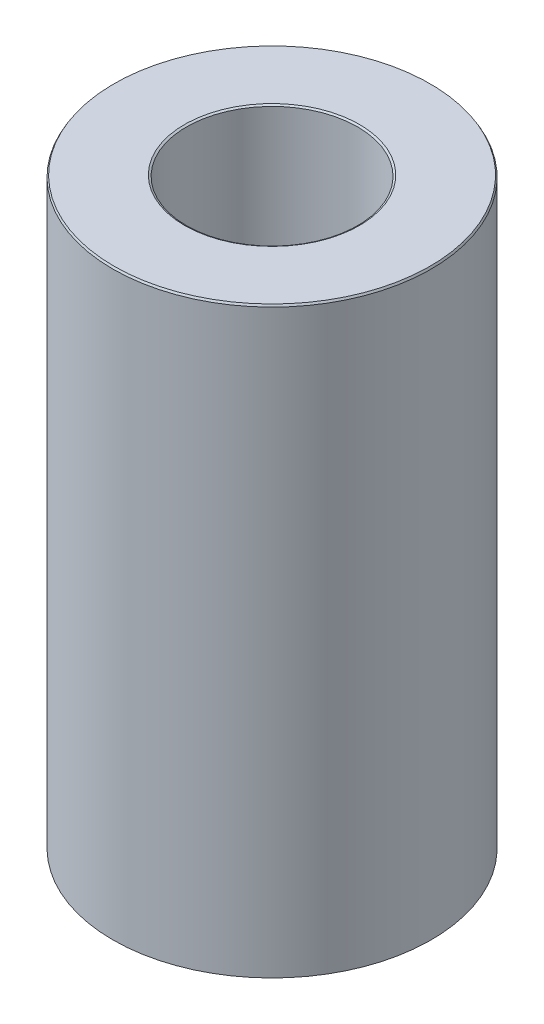
SolidWorks part; units mm, degrees
ref_plane "Front Plane" through (0, 0, 0) normal (0, 0, 1) x (1, 0, 0)
ref_plane "Top Plane" through (0, 0, 0) normal (0, 1, 0) x (1, 0, 0)
ref_plane "Right Plane" through (0, 0, 0) normal (1, 0, 0) x (0, 0, -1)
sketch "Sketch1" plane through (0, 0, 0) normal (0, 1, 0) x (1, 0, 0)
  circle A0 centre (0, 0) radius 52.5
  dimension "SLEEVE_OD" = 105
extrude "Boss-Extrude1" add sketch "Sketch1" along normal blind 192.6591
sketch "Sketch2" plane through (0, 0, 0) normal (0, 1, 0) x (1, 0, 0)
  circle A0 centre (0, 0) radius 28.2299
  dimension "BORE_D" = 56.4598
extrude "Cut-Extrude1" cut sketch "Sketch2" along normal through all
chamfer "Chamfer1" distance 0.633 angle 30 4 edges at (0, 192.6591, 28.2299) (0, 0, 28.2299) (0, 0, 52.5) (0, 192.6591, 52.5) first distance on face at (0, 192.6591, 28.2299) first distance on face at (0, 0, 28.2299) first distance on face at (0, 192.6591, 52.5)
